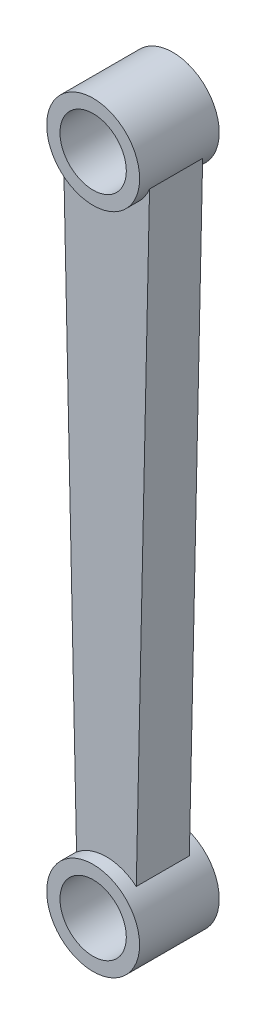
SolidWorks part; units mm, degrees
ref_plane "Front" through (0, 0, 0) normal (0, 0, 1) x (1, 0, 0)
ref_plane "Top" through (0, 0, 0) normal (0, 1, 0) x (1, 0, 0)
ref_plane "Right" through (0, 0, 0) normal (1, 0, 0) x (0, 0, -1)
sketch "Sketch1" plane through (0, 0, 0) normal (0, 0, 1) x (1, 0, 0)
  line L0 (0, 0) -> (0, -25) construction
  line L1 (-1.625, -0.6495) -> (-1.125, -23.6595)
  line L2 (1.625, -0.6495) -> (1.125, -23.6595)
  circle A0 centre (0, 0) radius 1.25
  arc A1 (1.625, -0.6495) -> (-1.625, -0.6495) centre (0, 0) ccw
  circle A2 centre (0, -25) radius 1.25
  arc A3 (-1.125, -23.6595) -> (1.125, -23.6595) centre (0, -25) ccw
  dimension "D1" = 2.25
  dimension "D2" = 3.5
  dimension "D3" = 3.25
  dimension "D4" = 3.5
  dimension "D6" = 2.5
  dimension "D7" = 1.75
  dimension "D5" = 25
ref_plane "Plane1" through (0, 0, 0) normal (0, 0, 1) x (1, 0, 0)
sketch "Sketch10" plane through (0, 0, 0) normal (0, 0, 1) x (1, 0, 0)
  circle A0 centre (0, 0) radius 1.25 construction
  circle A1 centre (0, 0) radius 1.25
  arc A2 (1.625, -0.6495) -> (-1.625, -0.6495) centre (0, 0) ccw construction
  circle A3 centre (0, 0) radius 1.75
  point P6 (-1.6212, -0.8235)
extrude "Boss-Extrude1" add sketch "Sketch10" along normal blind 1.5 and the other way blind 1.5
ref_plane "Plane2" through (0, 0, 0) normal (0, 0, 1) x (1, 0, 0)
sketch "Sketch11" plane through (0, 0, 0) normal (0, 0, 1) x (1, 0, 0)
  circle A0 centre (0, -25) radius 1.25 construction
  circle A1 centre (0, -25) radius 1.25
  arc A2 (-1.125, -23.6595) -> (1.125, -23.6595) centre (0, -25) ccw construction
  circle A3 centre (0, -25) radius 1.75
  point P6 (-0.8311, -23.4599)
extrude "Boss-Extrude12" add sketch "Sketch11" along normal blind 1.5 and the other way blind 1.5 separate body
extrude "Boss-Extrude13" add sketch "Sketch1" along normal blind 1 and the other way blind 1
